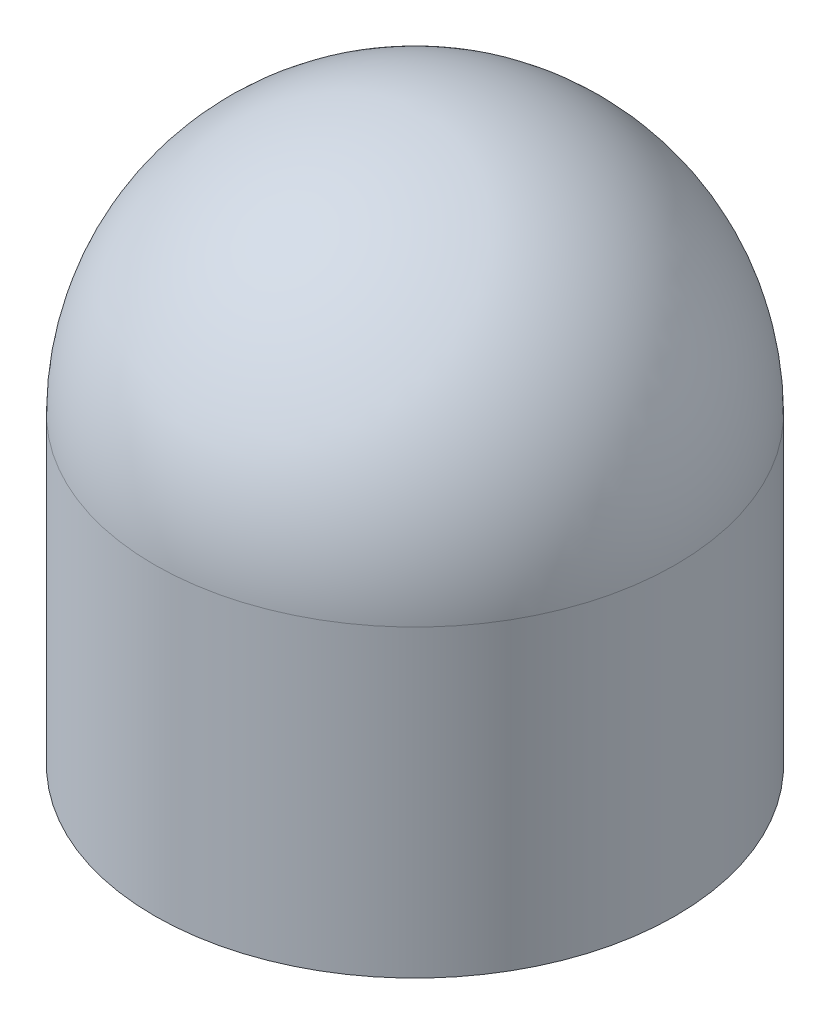
SolidWorks part; units mm, degrees
ref_plane "Front Plane" through (0, 0, 0) normal (0, 0, 1) x (1, 0, 0)
ref_plane "Top Plane" through (0, 0, 0) normal (0, 1, 0) x (1, 0, 0)
ref_plane "Right Plane" through (0, 0, 0) normal (1, 0, 0) x (0, 0, -1)
sketch "Sketch1" plane through (0, 0, 0) normal (0, 1, 0) x (1, 0, 0)
  circle A0 centre (0, 0) radius 1.5
  dimension "D1" = 3
extrude "Boss-Extrude1" add sketch "Sketch1" along normal blind 1.75
dome "Dome1" faces to dome 1 distance 1.5 reverse direction no elliptical dome no face at (0, 1.75, 1.5) parameters "D1"=1.5
